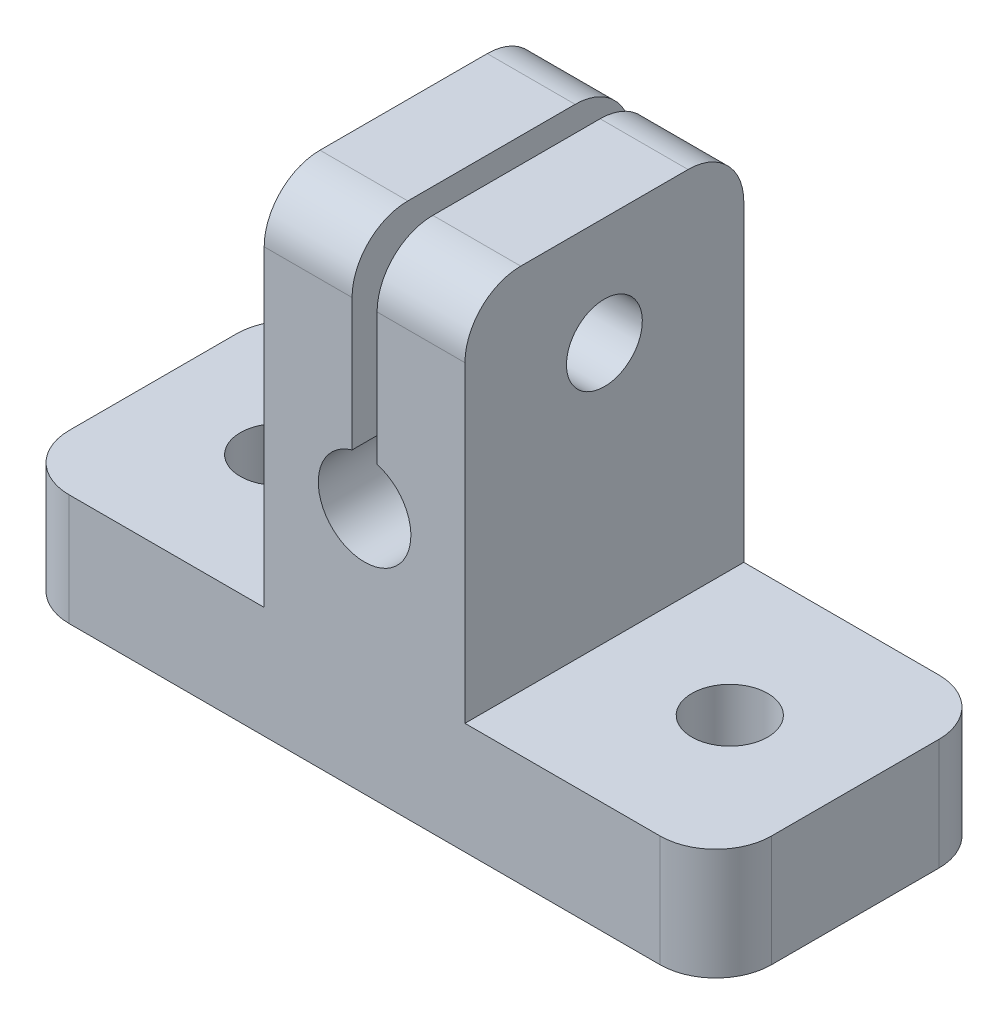
SolidWorks part; units mm, degrees
ref_plane "Front Plane" through (0, 0, 0) normal (0, 0, 1) x (1, 0, 0)
ref_plane "Top Plane" through (0, 0, 0) normal (0, 1, 0) x (1, 0, 0)
ref_plane "Right Plane" through (0, 0, 0) normal (1, 0, 0) x (0, 0, -1)
sketch "Sketch7" plane through (0, 0, 0) normal (0, 0, 1) x (1, 0, 0)
  line L0 (-42.3883, -20.8689) -> (-64.8745, -20.8689)
  line L1 (-33.3883, 12.1311) -> (-33.3883, -30.8689) construction
  line L2 (-24.3883, -20.8689) -> (-24.3883, 12.1311)
  line L3 (-24.3883, 12.1311) -> (-42.3883, 12.1311)
  line L4 (-42.3883, -20.8689) -> (-42.3883, 12.1311)
  line L7 (-1.9022, -30.8689) -> (-64.8745, -30.8689)
  line L8 (-1.9022, -30.8689) -> (-1.9022, -20.8689)
  line L9 (-1.9022, -20.8689) -> (-24.3883, -20.8689)
  line L10 (-64.8745, -30.8689) -> (-64.8745, -20.8689)
  dimension "D1" = 10
  dimension "D2" = 33
  dimension "D3" = 18
  dimension "D4" = 22.4861
extrude "Boss-Extrude3" add sketch "Sketch7" along normal blind 25
sketch "Sketch9" plane through (0, 0, 0) normal (0, 0, 1) x (1, 0, 0)
  line L0 (-64.8745, -30.8689) -> (-1.9022, -30.8689) construction
  line L1 (-33.3883, 12.1311) -> (-33.3883, -30.8689) construction
  line L2 (-24.3883, 12.1311) -> (-42.3883, 12.1311) construction
  line L3 (-64.8745, -30.8689) -> (-1.9022, -30.8689) construction
  circle A0 centre (-33.3883, -8.6989) radius 4.15
  dimension "D1" = 8.3
  dimension "D2" = 22.17
extrude "Cut-Extrude1" cut sketch "Sketch9" along normal up to surface (25 mm away) up to face at (-33.3883, -15.1189, 25)
sketch "Sketch10" plane through (0, -20.8689, 0) normal (0, 1, 0) x (-1, 0, 0)
  line L0 (13.1453, 0) -> (13.1453, 25) construction
  line L1 (1.9022, 0) -> (24.3883, 0) construction
  line L2 (1.9022, 25) -> (24.3883, 25) construction
  line L3 (24.3883, 12.5) -> (1.9022, 12.5) construction
  line L4 (24.3883, 25) -> (24.3883, 0) construction
  line L5 (1.9022, 25) -> (1.9022, 0) construction
  line L6 (53.6314, 0) -> (53.6314, 25) construction
  line L7 (42.3883, 0) -> (64.8745, 0) construction
  line L8 (42.3883, 25) -> (64.8745, 25) construction
  line L9 (64.8745, 12.5) -> (42.3883, 12.5) construction
  line L10 (64.8745, 25) -> (64.8745, 0) construction
  line L11 (42.3883, 25) -> (42.3883, 0) construction
  circle A0 centre (53.6314, 12.5) radius 3.4
  circle A1 centre (13.1453, 12.5) radius 3.4
  dimension "D1" = 6.8
  dimension "D2" = 6.8
extrude "Cut-Extrude2" cut sketch "Sketch10" against normal up to surface (10 mm away) up to face at (-33.3883, -30.8689, 12.5)
sketch "Sketch11" plane through (0, 0, 0) normal (0, 0, 1) x (1, 0, 0)
  line L0 (-33.3883, 12.1311) -> (-33.3883, -12.8489) construction
  line L1 (-24.3883, 12.1311) -> (-42.3883, 12.1311) construction
  line L2 (-34.5102, -4.7034) -> (-34.5102, 12.1311)
  line L3 (-34.5102, -4.7034) -> (-32.2665, -4.7034)
  line L4 (-34.5102, 12.1311) -> (-32.2665, 12.1311)
  line L5 (-32.2665, -4.7034) -> (-32.2665, 12.1311)
  line L6 (-34.5102, -4.7034) -> (-32.2665, 12.1311) construction
  line L7 (-34.5102, 12.1311) -> (-32.2665, -4.7034) construction
  circle A0 centre (-33.3883, -8.6989) radius 4.15 construction
  point P6 (-34.8883, -6.0694)
  point P9 (-33.3883, 3.7138)
extrude "Cut-Extrude3" cut sketch "Sketch11" along normal up to surface (25 mm away) up to face at (-29.2383, -8.6989, 25)
sketch "Sketch12" plane through (-42.3883, 0, 0) normal (-1, 0, 0) x (0, 0, 1)
  line L0 (12.5, 12.1311) -> (12.5, -30.8689) construction
  line L4 (25, 12.1311) -> (0, 12.1311) construction
  line L5 (25, -30.8689) -> (0, -30.8689) construction
  circle A0 centre (12.5, 2.4237) radius 3.4
  dimension "D1" = 6.8
extrude "Cut-Extrude4" cut sketch "Sketch12" against normal up to surface (18 mm away) up to face at (-24.3883, -4.3689, 12.5)
fillet "Fillet1" radius 5 8 edges at (-28.3274, 12.1311, 0) (-38.4493, 12.1311, 0) (-28.3274, 12.1311, 25) (-38.4493, 12.1311, 25) (-1.9022, -25.8689, 25) (-1.9022, -25.8689, 0) (-64.8745, -25.8689, 25) (-64.8745, -25.8689, 0)
